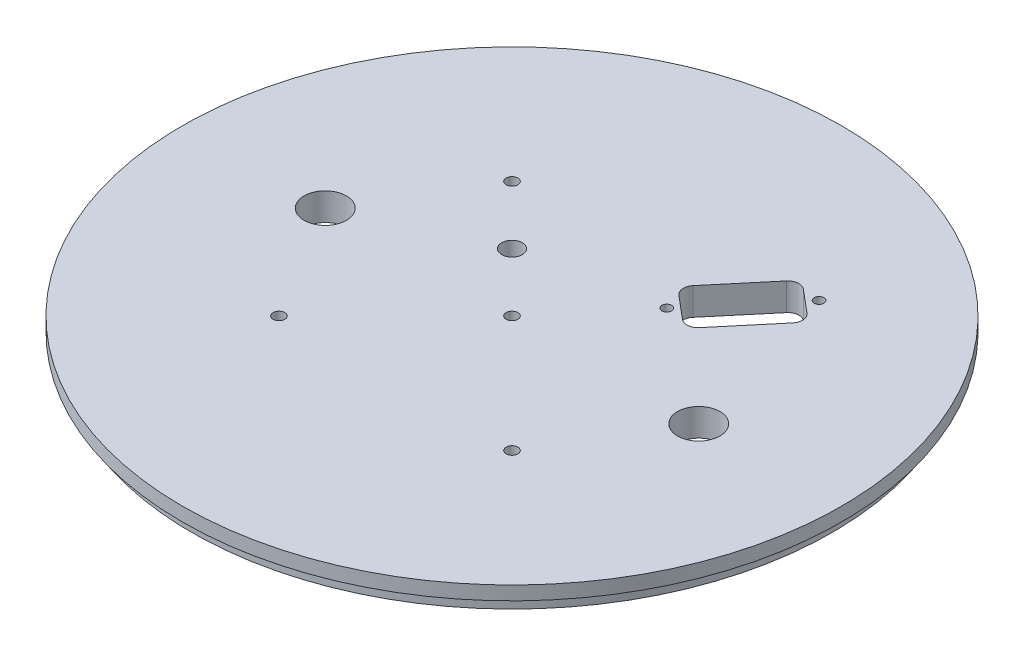
SolidWorks part; units mm, degrees
material "6061-T6 (SS)"
ref_plane "Front Plane" through (0, 0, 0) normal (0, 0, 1) x (1, 0, 0)
ref_plane "Top Plane" through (0, 0, 0) normal (0, 1, 0) x (1, 0, 0)
ref_plane "Right Plane" through (0, 0, 0) normal (1, 0, 0) x (0, 0, -1)
sketch "Sketch1" plane through (0, 0, 0) normal (0, 1, 0) x (1, 0, 0)
  line L0 (0, -76.2) -> (0, 76.2) construction
  line L1 (-76.2, 0) -> (76.2, 0) construction
  line L2 (-26.9408, 26.9408) -> (0, 0) construction
  line L3 (0, 56.7387) -> (0, 29.6936) construction
  line L4 (3.6407, 56.7387) -> (3.6407, 29.6936) construction
  line L5 (-3.6407, 56.7387) -> (-3.6407, 29.6936) construction
  line L6 (0, -56.7387) -> (0, -29.6936) construction
  line L7 (3.6407, -56.7387) -> (3.6407, -29.6936) construction
  line L8 (-3.6407, -56.7387) -> (-3.6407, -29.6936) construction
  line L9 (-53.8815, -53.8815) -> (54.3236, 54.3236) construction
  line L10 (-26.9408, -26.9408) -> (0, 0) construction
  circle A0 centre (0, 0) radius 76.2
  circle A1 centre (0, 0) radius 3.175 construction
  circle A2 centre (43.18, 0) radius 4.9022
  circle A3 centre (-43.18, 0) radius 4.9022
  circle A4 centre (-26.9408, 26.9408) radius 1.3589
  arc A6 (3.6407, 56.7387) -> (-3.6407, 56.7387) centre (0, 56.7387) ccw construction
  arc A7 (-3.6407, 29.6936) -> (3.6407, 29.6936) centre (0, 29.6936) ccw construction
  arc A8 (3.6407, -56.7387) -> (-3.6407, -56.7387) centre (0, -56.7387) cw construction
  arc A9 (-3.6407, -29.6936) -> (3.6407, -29.6936) centre (0, -29.6936) cw construction
  circle A10 centre (26.9408, -26.9408) radius 1.3589
  circle A11 centre (-13.4704, 13.4704) radius 2.3813
  circle A13 centre (-26.9408, -26.9408) radius 1.3589
  circle A14 centre (0, 0) radius 38.1 construction
  circle A15 centre (0, 0) radius 1.3589
  point P16 (0, 43.2162)
  point P19 (0, 0)
  point P26 (0, -43.2162)
  dimension "D1" = 152.4
  dimension "D2" = 6.35
  dimension "D3" = 9.8044
  dimension "D5" = 2.7178
  dimension "D8" = 4.7625
  dimension "D10" = 2.7178
  dimension "D12" = 2.7178
  dimension "D6" = 38.1
  dimension "D7" = 45
  dimension "D4" = 45
  dimension "D9" = 43.18
  dimension "D11" = 38.1
extrude "Boss-Extrude1" add sketch "Sketch1" along normal blind 6.35
sketch "Sketch2" plane through (0, 0, 0) normal (0, -1, 0) x (1, 0, 0)
  circle A0 centre (0, 0) radius 76.2
  circle A1 centre (0, 0) radius 74.041
  dimension "D1" = 152.4
  dimension "D2" = 148.082
extrude "Cut-Extrude1" cut sketch "Sketch2" against normal blind 3.175
sketch "Sketch3" plane through (0, 6.35, 0) normal (0, 1, 0) x (1, 0, 0)
  line L0 (0, 76.2) -> (0, -76.2) construction
  line L1 (-76.2, 0) -> (76.2, 0) construction
  line L2 (0, 34.798) -> (0, 13.97) construction
  line L3 (3.2385, 34.798) -> (3.2385, 13.97)
  line L4 (-3.2385, 34.798) -> (-3.2385, 13.97)
  line L5 (0, -34.798) -> (0, -13.97) construction
  line L6 (3.2385, -34.798) -> (3.2385, -13.97)
  line L7 (-3.2385, -34.798) -> (-3.2385, -13.97)
  circle A0 centre (0, 0) radius 76.2 construction
  arc A1 (3.2385, 34.798) -> (-3.2385, 34.798) centre (0, 34.798) ccw
  arc A2 (-3.2385, 13.97) -> (3.2385, 13.97) centre (0, 13.97) ccw
  arc A3 (3.2385, -34.798) -> (-3.2385, -34.798) centre (0, -34.798) cw
  arc A4 (-3.2385, -13.97) -> (3.2385, -13.97) centre (0, -13.97) cw
  point P7 (0, 13.97)
  point P8 (0, 34.798)
  point P12 (0, 24.384)
  point P20 (0, -24.384)
  point P25 (0, -34.798)
  point P26 (0, -13.97)
  dimension "D1" = 13.97
  dimension "D2" = 20.828
  dimension "D3" = 6.477
extrude "Cut-Extrude2" cut sketch "Sketch3" against normal blind 3.556 from offset 3.175 offset against normal yes
hole_wizard "Tap Drill for #4-40 Tap1" positions "Sketch5" profile "Sketch6" hole size "#4-40" standard "ANSI Inch" end condition through all
sketch "Sketch5" plane through (0, 6.35, 0) normal (0, 1, 0) x (1, 0, 0)
  line L0 (0, 0) -> (53.6567, 63.9455) construction
  line L2 (0, 0) -> (43.18, 0) construction
  point P0 (16.3268, 19.4575)
  point P2 (32.3965, 38.6086)
  dimension "D1" = 50
  dimension "D2" = 25
  dimension "D3" = 25.4
sketch "Sketch6" plane through (16.3268, 6.35, -19.4575) normal (1, 0, 0) x (0, 0, 1)
  line L0 (0, 0) -> (0, 6.35)
  line L1 (0, 6.35) -> (1.1303, 6.35)
  line L2 (1.1303, 6.35) -> (1.1303, 0)
  line L5 (1.1303, 0) -> (0, 0)
  line L11 (0, -6.35) -> (0, 107.95) construction
  dimension "Thru Hole Dia." = 2.2606
  dimension "Thru Hole Depth" = 6.35
sketch "Sketch4" plane through (0, 6.35, 0) normal (0, 1, 0) x (1, 0, 0)
  line L0 (15.1695, 23.4128) -> (20.423, 19.0046)
  line L1 (14.8564, 26.9913) -> (24.7219, 38.7485)
  line L2 (24.0014, 19.3177) -> (33.8669, 31.0749)
  line L3 (28.3003, 39.0616) -> (33.5538, 34.6533)
  line L4 (0, 0) -> (32.3965, 38.6086) construction
  circle A1 centre (16.3268, 19.4575) radius 1.1303 construction
  arc A2 (24.7219, 38.7485) -> (28.3003, 39.0616) centre (26.6676, 37.1158) cw
  arc A3 (33.8669, 31.0749) -> (33.5538, 34.6533) centre (31.9212, 32.7076) ccw
  arc A4 (20.423, 19.0046) -> (24.0014, 19.3177) centre (22.0557, 20.9503) ccw
  arc A5 (14.8564, 26.9913) -> (15.1695, 23.4128) centre (16.8021, 25.3586) ccw
  point P11 (17.7962, 21.2087)
  dimension "D4" = 2.54
  dimension "D1" = 2.286
  dimension "D2" = 2.286
  dimension "D3" = 11.938
extrude "Cut-Extrude3" cut sketch "Sketch4" against normal through all
equation "\"leadDist\"=1.5"
equation "\"Lead_Screw_Dist\"= 3.4in"
equation "\"D9@Sketch1\"=\"Lead_Screw_Dist\"/2"
equation "\"Lead_Screw_Diam\"= 0.386in"
equation "\"D3@Sketch1\"=\"Lead_Screw_Diam\""
equation "\"Bodytube_OD\"= 6.17in"
equation "\"Bodytube_ID\"= 5.998in"
equation "\"Motor_OD\"= 4in"
equation "\"Fwd_Tube_Length\"= 40in"
equation "\"Mid_Tube_Length\"= 1in"
equation "\"Aft_Section_Length\"= 39in"
equation "\"AB_Coupler_OD_Length\"= 1in"
equation "\"AB_Coupling_Section_Length\"= 0.375in"
equation "\"AB_Coupler_Length\"= \"AB_Coupler_OD_Length\" + \"AB_Coupling_Section_Length\" * 2"
equation "\"Cutout_Angle\"= 80"
equation "\"AB_Paddle_Height\"= 0.375in"
equation "\"AB_Coupler_Num_Screws\"= 4"
equation "\"Num_Cutouts\"= 3"
equation "\"AB_Coupler_OD\"= 6.17in"
equation "\"AB_Coupler_ID\"= 5.75in"
equation "\"AB_Coupler_Surface_Diameter\"= 5.998in"
equation "\"AB_Coupling_Screw_Diameter\"= 0.1065in"
equation "\"AB_Central_Bushing_Length\"= .4724in"
equation "\"Lead_Screw_Length\"= (\"Mid_Coupler_Length\" + 2*0.375in + 2*0.5in)"
equation "\"Paddle_Pin_Offset\"= .25in"
equation "\"Paddle_Pin_Radius\"= 2.25in"
equation "\"SS_Paddle_Pin_Radius\"= 2.25*0.66in"
equation "\"Paddle_Gear_OD\"= 3.2in"
equation "\"Drive_Gear_OD\"= 1.7in"
equation "\"Fwd_BKHD_From_Top\"= 18in"
equation "\"Fin_Thickness\"= .118in"
equation "\"Guiderail_Cutout_Diameter\"= 1.5in"
equation "\"DB9_Hole_Dist\"= 25mm"
equation "\"Airbrakes_Wire_Hole_Dia\"= .25in"
equation "\"Airbrakes_Wire_Hole_Dist\"= 1.1in"
equation "\"Servo_Gear_Offset\"= 0.5in"
equation "\"Mid_Coupler_Length\"= 13in"
equation "\"D2@Sketch5\"=\"DB9_Hole_Dist\""
equation "\"DB9_Relief_Width\"= 0.47in"
equation "\"DB9_Relief_Hole_Offset\"= 0.09in"
equation "\"D1@Sketch4\"=\"DB9_Relief_Hole_Offset\""
equation "\"D2@Sketch4\"=\"DB9_Relief_Hole_Offset\""
equation "\"D3@Sketch4\"=\"DB9_Relief_Width\""
